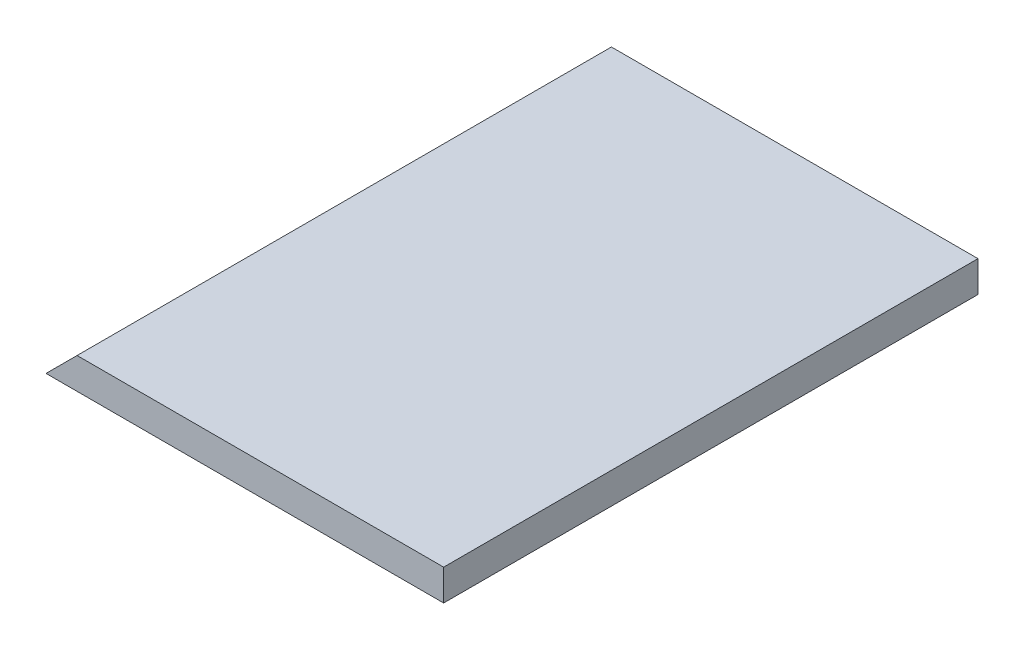
SolidWorks part; units mm, degrees
ref_plane "Front Plane" through (0, 0, 0) normal (0, 0, 1) x (1, 0, 0)
ref_plane "Top Plane" through (0, 0, 0) normal (0, 1, 0) x (1, 0, 0)
ref_plane "Right Plane" through (0, 0, 0) normal (1, 0, 0) x (0, 0, -1)
sketch "Sketch1" plane through (0, 0, 0) normal (0, 1, 0) x (1, 0, 0)
  line L1 (0, 0) -> (8.128, 0)
  line L2 (0, 0) -> (0, 10.922)
  line L3 (0, 10.922) -> (8.128, 10.922)
  line L4 (8.128, 0) -> (8.128, 10.922)
  dimension "D1" = 8.128
  dimension "D2" = 10.922
extrude "Boss-Extrude1" add sketch "Sketch1" along normal blind 0.635
chamfer "Chamfer1" distance 0.635 angle 45 1 edges at (0, 0.635, -5.461)
